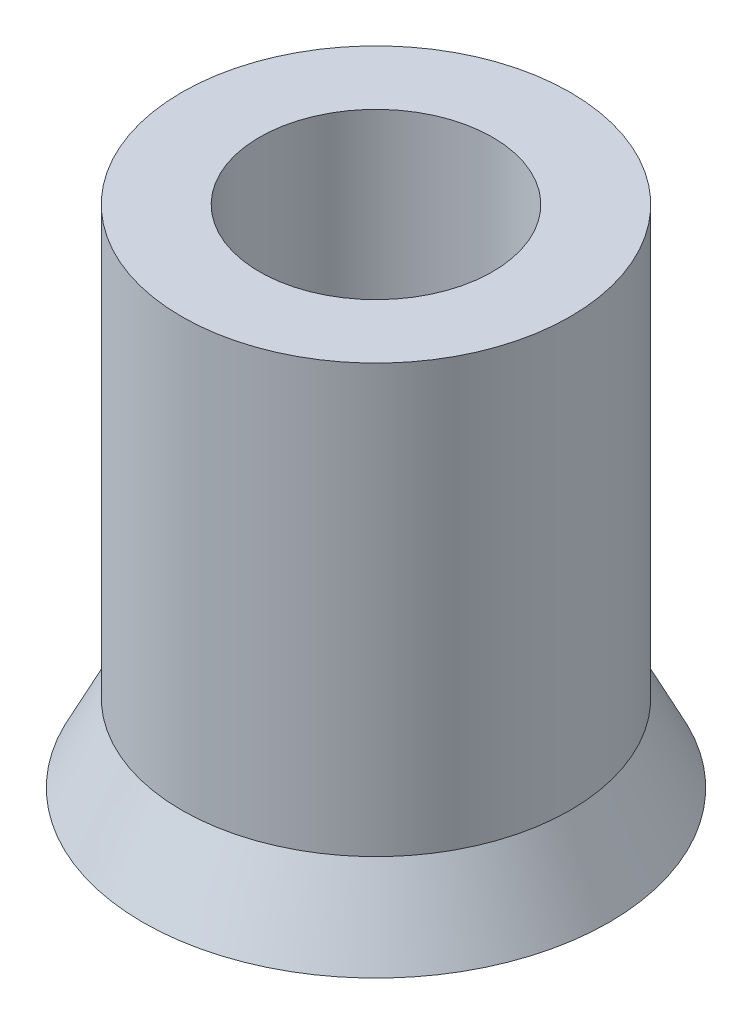
SolidWorks part; units mm, degrees
ref_plane "前视基准面" through (0, 0, 0) normal (0, 0, 1) x (1, 0, 0)
ref_plane "上视基准面" through (0, 0, 0) normal (0, 1, 0) x (1, 0, 0)
ref_plane "右视基准面" through (0, 0, 0) normal (1, 0, 0) x (0, 0, -1)
other "Configuration Table"
sketch "草图1" plane through (0, 0, 0) normal (0, 1, 0) x (1, 0, 0)
  circle A0 centre (0, 0) radius 3
  circle A1 centre (0, 0) radius 6
  circle A2 centre (0, 0) radius 5
  dimension "D1" = 6
  dimension "D2" = 12
  dimension "D3" = 10
extrude "凸台-拉伸1" add sketch "草图1" along normal blind 13 contours A2 A0 region at (-4.8586, 0, 0)
extrude "凸台-拉伸2" add sketch "草图1<3>" along normal blind 2 contours A1 A2 region at (-5.8303, 0, 0)
sketch "草图1<3>" plane through (0, 0, 0) normal (0, 1, 0) x (1, 0, 0) same geometry as "草图1"
chamfer "倒角1" distance 2 distance2 1 1 edges at (0, 2, 6) first distance on face at (0, 2, 6)
